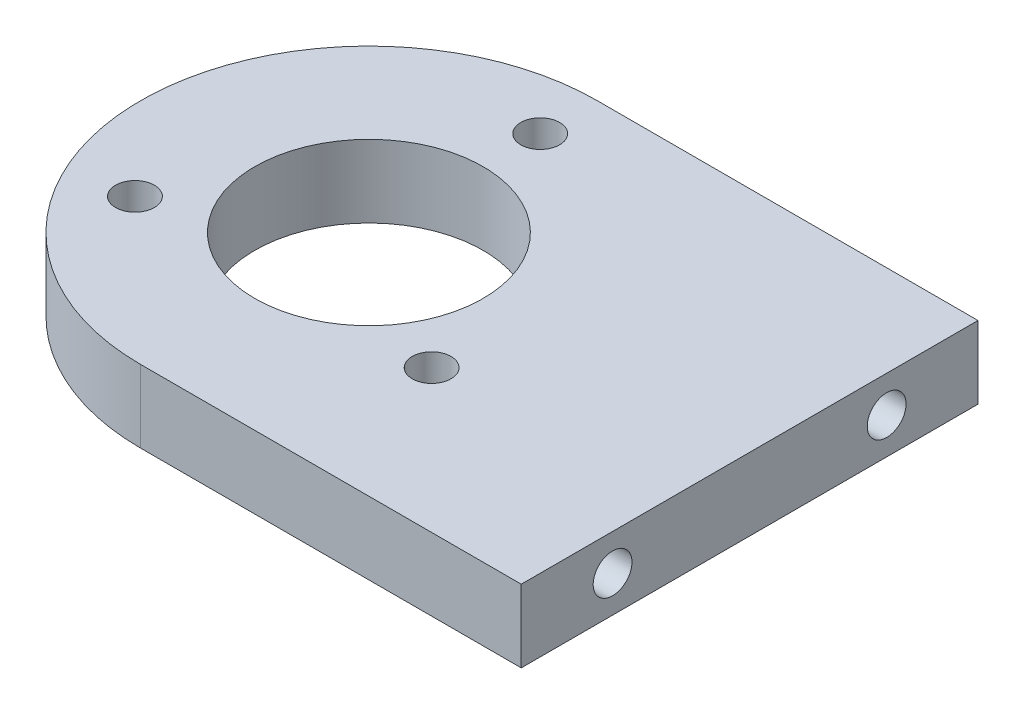
SolidWorks part; units mm, degrees
material "1060 Alloy"
ref_plane "Front Plane" through (0, 0, 0) normal (0, 0, 1) x (1, 0, 0)
ref_plane "Top Plane" through (0, 0, 0) normal (0, 1, 0) x (1, 0, 0)
ref_plane "Right Plane" through (0, 0, 0) normal (1, 0, 0) x (0, 0, -1)
sketch "Sketch1" plane through (0, 0, 0) normal (0, 1, 0) x (1, 0, 0)
  line L0 (33.34, 20) -> (33.34, -20)
  line L1 (0, 0) -> (94.428, 0) construction
  line L2 (0, 20) -> (33.34, 20)
  line L3 (0, -20) -> (33.34, -20)
  circle A0 centre (0, 0) radius 10
  arc A1 (0, 20) -> (0, -20) centre (0, 0) ccw
  circle A3 centre (0, 0) radius 20 construction
  point P5 (19.1261, 5.8474)
  point P7 (0, 20)
  point P9 (0, -20)
  dimension "D1" = 20
  dimension "D2" = 10
extrude "Boss-Extrude1" add sketch "Sketch1" along normal blind 6.35
hole_wizard "M3 Clearance Hole1" positions "Sketch2" profile "Sketch3" hole size "M3" standard "ANSI Metric" end condition through all
sketch "Sketch2" plane through (0, 6.35, 0) normal (0, 1, 0) x (1, 0, 0)
  circle A0 centre (0, 0) radius 15 construction
  point P0 (0, 15)
  point P14 (12.9919, -7.4991)
  point P15 (-12.9889, -7.5009)
  point P16 (0.001, 0)
  dimension "D2" = 30
  dimension "D1" = 15
  dimension "D3" = 3
sketch "Sketch3" plane through (0, 6.35, -15) normal (1, 0, 0) x (0, 0, 1)
  line L0 (0, 0) -> (0, 6.35)
  line L1 (0, 6.35) -> (1.7, 6.35)
  line L2 (1.7, 6.35) -> (1.7, 0)
  line L5 (1.7, 0) -> (0, 0)
  line L11 (0, -6.35) -> (0, 107.95) construction
  dimension "Thru Hole Dia." = 3.4
  dimension "Thru Hole Depth" = 6.35
hole_wizard "M3 Clearance Hole2" positions "Sketch6" profile "Sketch7" hole size "M3" standard "ANSI Metric"
sketch "Sketch6" plane through (33.34, 0, 0) normal (1, 0, 0) x (0, 0, -1)
  line L3 (20, 3.175) -> (-20, 3.175) construction
  line L4 (20, 6.35) -> (20, 0) construction
  line L5 (-20, 6.35) -> (-20, 0) construction
  point P0 (12, 3.175)
  point P2 (-12, 3.175)
  point P22 (0, 0)
  dimension "D2" = 12
  dimension "D3" = 12
sketch "Sketch7" plane through (33.34, 3.175, -12) normal (0, 1, 0) x (0, 0, -1)
  line L0 (0, 0) -> (0, 8.0215)
  line L1 (0, 8.0215) -> (1.7, 7)
  line L2 (1.7, 7) -> (1.7, 0)
  line L5 (1.7, 0) -> (0, 0)
  line L10 (0, 8.0215) -> (-1.7, 7) construction
  line L11 (0, -6.35) -> (0, 107.95) construction
  dimension "Hole Dia." = 3.4
  dimension "Hole Depth" = 7
  dimension "Drill Angle" = 118
